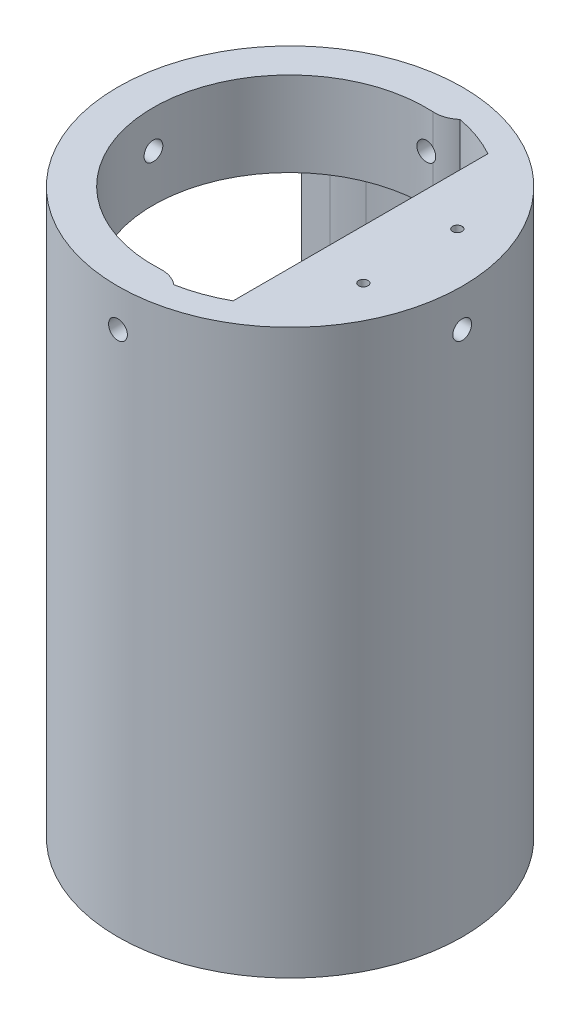
SolidWorks part; units mm, degrees
ref_plane "Front Plane" through (0, 0, 0) normal (0, 0, 1) x (1, 0, 0)
ref_plane "Top Plane" through (0, 0, 0) normal (0, 1, 0) x (1, 0, 0)
ref_plane "Right Plane" through (0, 0, 0) normal (1, 0, 0) x (0, 0, -1)
sketch "Sketch1" plane through (0, 0, 0) normal (0, 1, 0) x (1, 0, 0)
  circle A1 centre (0, 0) radius 46.609
  dimension "D1" = 93.218
extrude "Boss-Extrude1" add sketch "Sketch1" along normal blind 17.78
sketch "Sketch4" plane through (0, 17.78, 0) normal (0, 1, 0) x (1, 0, 0)
  line L0 (19.05, 42.5382) -> (19.05, -42.5382)
  circle A0 centre (0, 0) radius 46.609 construction
  arc A1 (19.05, 42.5382) -> (19.05, -42.5382) centre (0, 0) cw
  dimension "D1" = 19.05
extrude "Boss-Extrude2" add sketch "Sketch4" along normal blind 134.62
sketch "Sketch5" plane through (19.05, 0, 0) normal (-1, 0, 0) x (0, 0, 1)
  line L0 (-42.5382, 152.4) -> (42.5382, 152.4) construction
  line L1 (-26.67, 113.03) -> (26.67, 113.03)
  line L2 (-26.67, 113.03) -> (-26.67, 22.86)
  line L3 (-26.67, 22.86) -> (26.67, 22.86)
  line L4 (26.67, 113.03) -> (26.67, 22.86)
  line L5 (-25.879, 112.0381) -> (-25.4014, 113.03)
  line L6 (-25.4014, 113.03) -> (-25.879, 114.0219)
  line L7 (-25.879, 114.0219) -> (-26.9523, 114.2668)
  line L8 (-26.9523, 114.2668) -> (-27.813, 113.5804)
  line L9 (-27.813, 113.5804) -> (-27.813, 112.4796)
  line L10 (-27.813, 112.4796) -> (-26.9523, 111.7932)
  line L11 (-26.9523, 111.7932) -> (-25.879, 112.0381)
  line L12 (-42.5382, 17.78) -> (42.5382, 17.78) construction
  line L13 (27.9072, 113.03) -> (27.5448, 113.9048)
  line L14 (27.5448, 113.9048) -> (26.67, 114.2672)
  line L15 (26.67, 114.2672) -> (25.7952, 113.9048)
  line L16 (25.7952, 113.9048) -> (25.4328, 113.03)
  line L17 (25.4328, 113.03) -> (25.7952, 112.1552)
  line L18 (25.7952, 112.1552) -> (26.67, 111.7928)
  line L19 (26.67, 111.7928) -> (27.5448, 112.1552)
  line L20 (27.5448, 112.1552) -> (27.9072, 113.03)
  line L21 (-25.4328, 22.86) -> (-25.7952, 23.7348)
  line L22 (-25.7952, 23.7348) -> (-26.67, 24.0972)
  line L23 (-26.67, 24.0972) -> (-27.5448, 23.7348)
  line L24 (-27.5448, 23.7348) -> (-27.9072, 22.86)
  line L25 (-27.9072, 22.86) -> (-27.5448, 21.9852)
  line L26 (-27.5448, 21.9852) -> (-26.67, 21.6228)
  line L27 (-26.67, 21.6228) -> (-25.7952, 21.9852)
  line L28 (-25.7952, 21.9852) -> (-25.4328, 22.86)
  line L29 (27.9072, 22.86) -> (27.5448, 23.7348)
  line L30 (27.5448, 23.7348) -> (26.67, 24.0972)
  line L31 (26.67, 24.0972) -> (25.7952, 23.7348)
  line L32 (25.7952, 23.7348) -> (25.4328, 22.86)
  line L33 (25.4328, 22.86) -> (25.7952, 21.9852)
  line L34 (25.7952, 21.9852) -> (26.67, 21.6228)
  line L35 (26.67, 21.6228) -> (27.5448, 21.9852)
  line L36 (27.5448, 21.9852) -> (27.9072, 22.86)
  circle A4 centre (-26.67, 113.03) radius 1.143 construction
  circle A5 centre (26.67, 113.03) radius 1.143 construction
  circle A6 centre (-26.67, 22.86) radius 1.143 construction
  circle A7 centre (26.67, 22.86) radius 1.143 construction
  point P4 (0, 113.03)
  point P7 (0, 152.4)
  dimension "D5" = 2.286
  dimension "D6" = 2.286
  dimension "D7" = 2.286
  dimension "D8" = 2.286
  dimension "D1" = 0
  dimension "D2" = 5.08
  dimension "D3" = 90.17
  dimension "D4" = 53.34
sketch "Sketch9" plane through (0, 152.4, 0) normal (0, 1, 0) x (1, 0, 0)
  circle A0 centre (0, 0) radius 46.609
  circle A1 centre (0, 0) radius 39.37
  dimension "D1" = 93.218
  dimension "D2" = 78.74
extrude "Boss-Extrude5" add sketch "Sketch9" against normal up to surface (134.62 mm away) up to face at (-13.7795, 17.78, 0)
sketch "Sketch11" plane through (19.05, 0, 0) normal (-1, 0, 0) x (0, 0, 1)
  line L0 (-34.4542, 17.78) -> (-34.4542, 152.4) construction
  line L1 (-34.4542, 220.6179) -> (34.4542, 220.6179)
  line L2 (-34.4542, 220.6179) -> (-34.4542, 50.4379)
  line L3 (-34.4542, 50.4379) -> (34.4542, 50.4379)
  line L4 (34.4542, 220.6179) -> (34.4542, 50.4379)
  line L5 (34.4542, 152.4) -> (34.4542, 17.78) construction
  line L6 (-34.4542, 17.78) -> (34.4542, 17.78) construction
  line L7 (-34.4542, 154.94) -> (34.4542, 154.94)
  line L8 (-34.4542, 154.94) -> (-34.4542, 129.54)
  line L9 (-34.4542, 129.54) -> (34.4542, 129.54)
  line L10 (34.4542, 154.94) -> (34.4542, 129.54)
  line L12 (-34.4542, 50.4379) -> (34.4542, 50.4379)
  line L13 (-34.4542, 50.4379) -> (-34.4542, 17.78)
  line L14 (-34.4542, 17.78) -> (34.4542, 17.78)
  line L15 (34.4542, 50.4379) -> (34.4542, 17.78)
  dimension "D1" = 25.4
  dimension "D2" = 137.16
  dimension "D3" = 170.18
extrude "Cut-Extrude3" cut sketch "Sketch11" along normal blind 154.686
sketch "Sketch12" plane through (19.05, 0, 0) normal (-1, 0, 0) x (0, 0, 1)
  line L0 (-34.4542, 17.78) -> (34.4542, 17.78) construction
  line L1 (-31.75, 147.32) -> (31.75, 147.32)
  line L2 (-31.75, 147.32) -> (-31.75, 121.92)
  line L3 (-31.75, 121.92) -> (31.75, 121.92)
  line L4 (31.75, 147.32) -> (31.75, 121.92)
  point P0 (0, 121.92)
  dimension "D1" = 25.4
  dimension "D2" = 0
  dimension "D3" = 63.5
  dimension "D4" = 104.14
sketch "Sketch13" plane through (0, 152.4, 0) normal (0, 1, 0) x (1, 0, 0)
  circle A0 centre (32.512, 0) radius 3.0803
  circle A1 centre (32.512, -12.7) radius 1.27
  circle A2 centre (32.512, 12.7) radius 1.27
  dimension "D4" = 2.54
  dimension "D5" = 2.54
  dimension "D1" = 12.7
  dimension "D2" = 12.7
  dimension "D3" = 0
  dimension "D6" = 32.512
extrude "Cut-Extrude4" cut sketch "Sketch13" against normal blind 12.7 contours A1 | A2
extrude "Cut-Extrude5" cut sketch "Sketch12" against normal blind 5.08
extrude "Cut-Extrude6" cut sketch "Sketch5" against normal blind 2.54 contours L35 L36 L29 L30 L4 L3 L33 L34 | L19 L20 L13 L14 L15 L16 L1 L4 | L17 L18 L4 L1 | L10 L11 L2 L1 L6 L7 L8 L9 | L2 L11 L5 L1 | L21 L22 L2 L3 | L27 L28 L3 L2 L23 L24 L25 L26 | L31 L32 L3 L4
fillet "Fillet1" radius 1.27 1 edges at (-46.609, 17.78, 0)
fillet "Fillet2" radius 20.32 2 edges at (-19.05, 73.66, -34.4542) (-19.05, 73.66, 34.4542)
sketch "Sketch16" plane through (0, 152.4, 0) normal (0, 1, 0) x (1, 0, 0)
  line L2 (7.24, 38.6986) -> (7.24, -38.6986)
  arc A0 (19.05, 34.4542) -> (19.05, -34.4542) centre (0, 0) ccw construction
  arc A1 (0, 39.37) -> (0, -39.37) centre (0, 0) ccw
  arc A2 (7.24, 36.1586) -> (7.24, -36.1586) centre (-0.1301, 0) ccw
  arc A3 (-15.6457, -36.1277) -> (19.05, -34.4542) centre (0, 0) ccw construction
  arc A4 (7.24, 38.6986) -> (7.24, -38.6986) centre (0, 0) ccw
  dimension "D1" = 2.54
  dimension "D2" = 2.54
extrude "Boss-Extrude6" add sketch "Sketch16" against normal up to surface (22.86 mm away) up to face at (-30.0474, 129.54, 0)
sketch "Sketch15" plane through (0, 0, 0) normal (0, 0, 1) x (1, 0, 0)
  line L0 (19.05, 152.4) -> (7.24, 152.4) construction
  circle A0 centre (0, 142.24) radius 2.54
  dimension "D1" = 5.08
  dimension "D2" = 10.16
extrude "Cut-Extrude8" cut sketch "Sketch15" against normal up to surface and the other way up to surface
sketch "Sketch14" plane through (0, 0, 0) normal (1, 0, 0) x (0, 0, -1)
  line L0 (38.6986, 152.4) -> (34.4542, 152.4) construction
  circle A0 centre (0, 142.24) radius 2.54
  dimension "D1" = 5.08
  dimension "D2" = 10.16
extrude "Cut-Extrude7" cut sketch "Sketch14" against normal up to surface and the other way up to surface up to face at (-2.4729, 142.82, -46.5434) other way up to face at (-2.4729, 142.82, -46.5434)
fillet "Fillet4" radius 7.62 2 edges at (7.24, 140.97, 36.1586) (7.24, 140.97, -36.1586)
